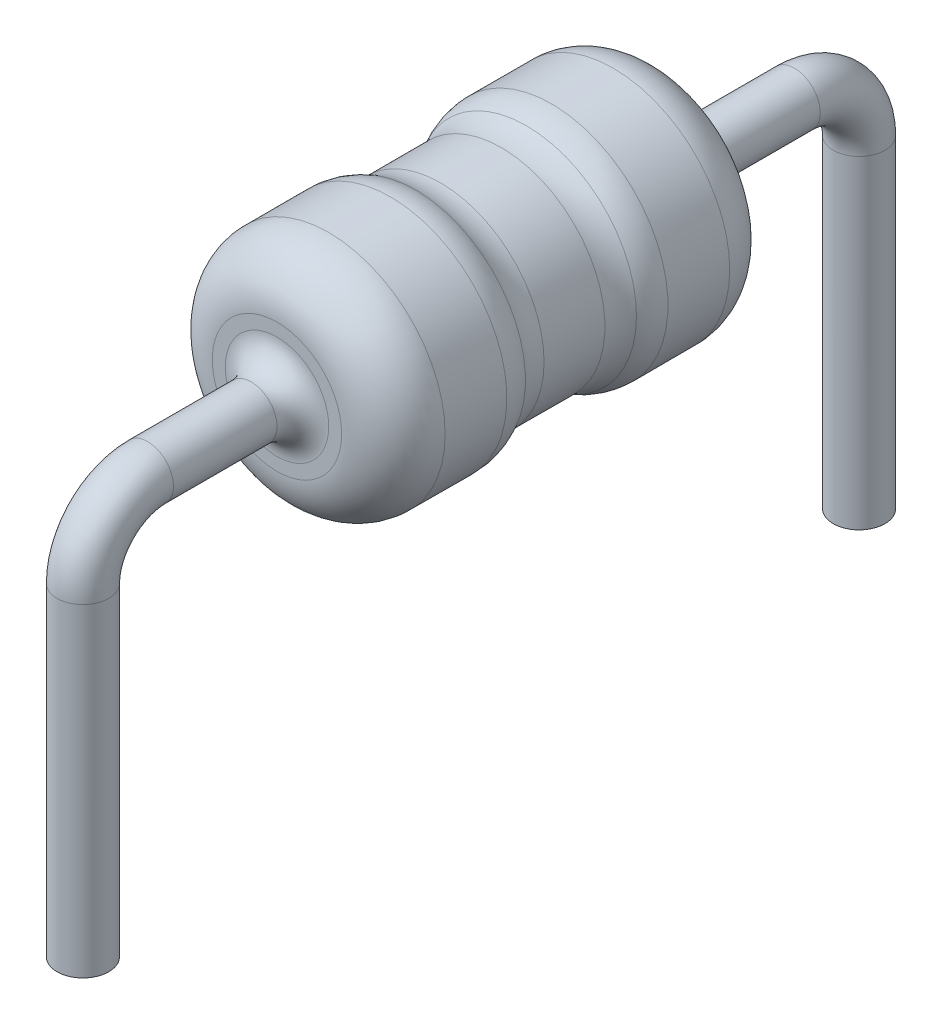
SolidWorks part; units mm, degrees
ref_plane "Ön Düzlem" through (0, 0, 0) normal (0, 0, 1) x (1, 0, 0)
ref_plane "Üst Düzlem" through (0, 0, 0) normal (0, 1, 0) x (1, 0, 0)
ref_plane "Sağ Düzlem" through (0, 0, 0) normal (1, 0, 0) x (0, 0, -1)
sketch "Çizim1" plane through (0, 0, 0) normal (0, 0, 1) x (1, 0, 0)
  circle A0 centre (0, 0) radius 0.9
extrude "Yükseklik-Ekstrüzyon1" add sketch "Çizim1" along normal blind 1
sketch "Çizim2" plane through (0, 0, 1) normal (0, 0, 1) x (1, 0, 0)
  circle A0 centre (0, 0) radius 0.8
extrude "Yükseklik-Ekstrüzyon2" add sketch "Çizim2" along normal blind 1
sketch "Çizim3" plane through (0, 0, 2) normal (0, 0, 1) x (1, 0, 0)
  circle A0 centre (0, 0) radius 0.9
extrude "Yükseklik-Ekstrüzyon3" add sketch "Çizim3" along normal blind 1
sketch "Çizim4" plane through (0, 0, 0) normal (1, 0, 0) x (0, 0, -1)
  line L0 (-2.8153, 0) -> (-4, 0)
  line L1 (-4.5, -0.5) -> (-4.5, -3)
  line L2 (-3, 0.9) -> (-3, -0.9) construction
  arc A0 (-4.5, -0.5) -> (-4, 0) centre (-4, -0.5) cw
  point P8 (-4.5, 0)
  dimension "D3" = 0.5
  dimension "D1" = 1.5
  dimension "D2" = 3
ref_plane "Düzlem1" through (0, 0, 2.8153) normal (0, 0, 1) x (1, 0, 0)
sketch "Çizim5" plane through (0, 0, 2.8153) normal (0, 0, 1) x (1, 0, 0)
  circle A0 centre (0, 0) radius 0.2
sweep "Süpür1" add profiles "Çizim5" path "Çizim4"
sketch "Çizim6" plane through (0, 0, 0) normal (1, 0, 0) x (0, 0, -1)
  line L0 (1, 0) -> (-0.3548, 0)
  line L1 (1.5, -0.5) -> (1.5, -3)
  line L2 (0, -0.9) -> (0, 0.9) construction
  arc A0 (1.5, -0.5) -> (1, 0) centre (1, -0.5) ccw
  point P6 (2.3, 0)
  dimension "D3" = 0.5
  dimension "D1" = 3
  dimension "D2" = 1.5
ref_plane "Düzlem2" through (0, 0, 0.3548) normal (0, 0, -1) x (-1, 0, 0)
sketch "Çizim7" plane through (0, 0, 0.3548) normal (0, 0, -1) x (-1, 0, 0)
  circle A0 centre (0, 0) radius 0.2
sweep "Süpür2" add profiles "Çizim7" path "Çizim6"
fillet "Radyus1" radius 0.4 2 edges at (0.8, 0, 1) (0.8, 0, 2)
fillet "Radyus2" radius 0.4 2 edges at (0.9, 0, 0) (0.9, 0, 1)
fillet "Radyus3" radius 0.4 2 edges at (0.9, 0, 2) (0.9, 0, 3)
fillet "Radyus4" radius 0.2 1 edges at (0.2, 0, 3)
fillet "Radyus5" radius 0.2 1 edges at (0.2, 0, 0)
